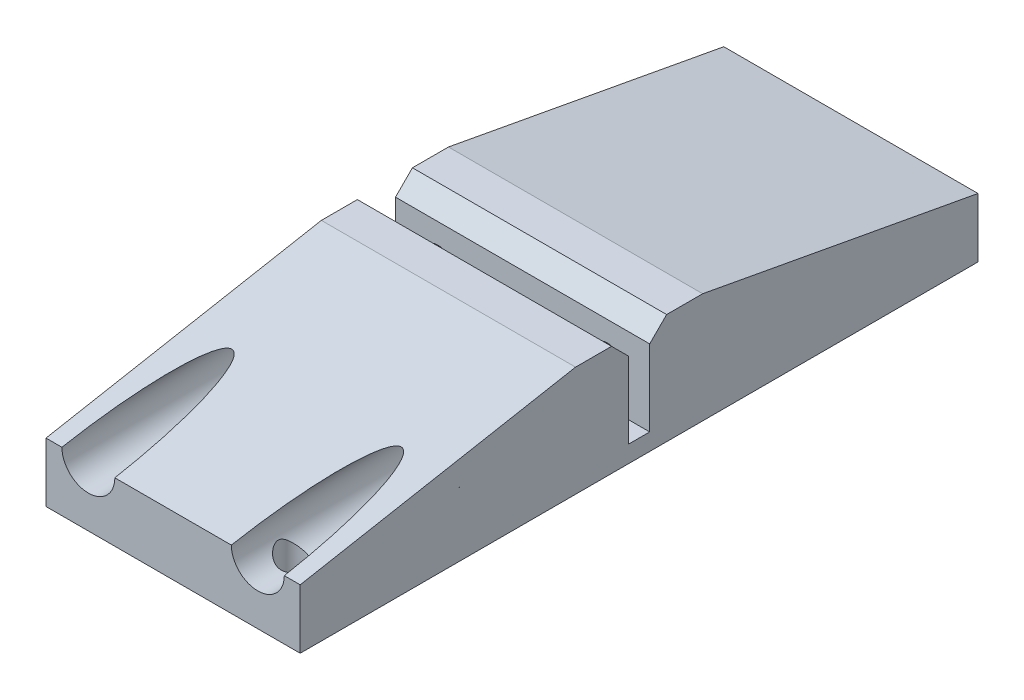
SolidWorks part; units mm, degrees
ref_plane "Front Plane" through (0, 0, 0) normal (0, 0, 1) x (1, 0, 0)
ref_plane "Top Plane" through (0, 0, 0) normal (0, 1, 0) x (1, 0, 0)
ref_plane "Right Plane" through (0, 0, 0) normal (1, 0, 0) x (0, 0, -1)
sketch "Sketch1" plane through (0, 0, 0) normal (0, 1, 0) x (1, 0, 0)
  line L0 (-19.05, 44.45) -> (19.05, 44.45) construction
  line L1 (-19.05, 50.8) -> (19.05, 50.8)
  line L2 (-19.05, 50.8) -> (-19.05, -50.8)
  line L3 (-19.05, -50.8) -> (19.05, -50.8)
  line L4 (19.05, 50.8) -> (19.05, -50.8)
  line L5 (-19.05, 50.8) -> (19.05, -50.8) construction
  line L6 (-19.05, -50.8) -> (19.05, 50.8) construction
  line L7 (19.05, -44.45) -> (-19.05, -44.45) construction
  circle A0 centre (-1.27, 44.45) radius 2.032
  circle A1 centre (11.43, 44.45) radius 2.032
  circle A2 centre (-1.27, -44.45) radius 2.032
  circle A3 centre (11.43, -44.45) radius 2.032
  point P0 (0, 0)
  dimension "D5" = 4.064
  dimension "D6" = 12.7
  dimension "D7" = 17.78
  dimension "D8" = 12.7
  dimension "D9" = 17.78
  dimension "D1" = 101.6
  dimension "D2" = 38.1
  dimension "D3" = 6.35
  dimension "D4" = 6.35
extrude "Boss-Extrude1" add sketch "Sketch1" along normal blind 16.51 contours L2 L3 L4 L1
extrude "Cut-Extrude1" cut sketch "Sketch1<3>" along normal blind 9.525 contours A2 | A0 | A1 | A3
sketch "Sketch1<3>" plane through (0, 0, 0) normal (0, 1, 0) x (1, 0, 0) same geometry as "Sketch1"
sketch "Sketch2" plane through (19.05, 0, 0) normal (1, 0, 0) x (0, 0, -1)
  line L0 (-50.8, 8.89) -> (-9.525, 16.51)
  line L1 (-50.8, 16.51) -> (-50.8, 0) construction
  line L2 (50.8, 16.51) -> (-50.8, 16.51) construction
  line L3 (9.525, 16.51) -> (50.8, 8.89)
  line L4 (50.8, 16.51) -> (50.8, 0) construction
  line L11 (-50.8, 8.89) -> (-50.8, 0)
  line L12 (50.8, 8.89) -> (50.8, 0)
  line L15 (-50.8, 0) -> (50.8, 0)
  line L16 (50.8, 0) -> (50.8, 16.51)
  line L17 (50.8, 16.51) -> (-50.8, 16.51)
  line L18 (-50.8, 16.51) -> (-50.8, 0)
  line L19 (-50.8, 0) -> (50.8, 0)
  line L20 (50.8, 0) -> (50.8, 16.51)
  line L21 (50.8, 16.51) -> (-50.8, 16.51)
  line L22 (-50.8, 16.51) -> (-50.8, 0)
  line M8 (50.8, 0) -> (50.8, 16.51)
  line M9 (50.8, 16.51) -> (-50.8, 16.51)
  line M10 (-50.8, 16.51) -> (-50.8, 0)
  dimension "D1" = 19.05
  dimension "D2" = 8.89
  dimension "D4" = 0
extrude "Cut-Extrude2" cut sketch "Sketch2" against normal through all and the other way through all contours L0 M10 M9 | L3 M9 M8 region at (19.05, 13.97, 37.0417) region at (19.05, 13.97, -37.0417)
sketch "Sketch3" plane through (0, 16.51, 0) normal (0, 1, 0) x (1, 0, 0)
  line L0 (19.05, 0) -> (-19.05, 0) construction
  line L1 (19.05, 1.5875) -> (-19.05, 1.5875)
  line L2 (19.05, -1.5875) -> (-19.05, -1.5875)
  line L4 (-19.05, 9.525) -> (-19.05, -9.525)
  line L5 (-19.05, -9.525) -> (19.05, -9.525)
  line L6 (19.05, -9.525) -> (19.05, 9.525)
  line L7 (19.05, 9.525) -> (-19.05, 9.525)
  line L8 (-19.05, 9.525) -> (-19.05, -9.525)
  line L9 (-19.05, -9.525) -> (19.05, -9.525)
  line L10 (19.05, -9.525) -> (19.05, 9.525)
  line L11 (19.05, 9.525) -> (-19.05, 9.525)
  line M6 (-19.05, 9.525) -> (-19.05, -9.525)
  line M8 (19.05, -9.525) -> (19.05, 9.525)
  dimension "D1" = 0
  dimension "D2" = 1.5875
  dimension "D3" = 1.5875
extrude "Cut-Extrude3" cut sketch "Sketch3" against normal blind 13.97 contours L0 L10 L1 M6 | L0 L8 L2 M8 region at (0, 16.51, 0.7938) region at (0, 16.51, -0.7937)
chamfer "Chamfer1" distance 2.54 angle 45 2 edges at (0, 16.51, 1.5875) (0, 16.51, -1.5875)
sketch "Sketch5" plane through (0, 0, -1.5875) normal (0, 0, 1) x (1, 0, 0)
  line L0 (-19.05, 8.89) -> (19.05, 8.89)
  line L4 (19.05, 2.54) -> (19.05, 13.97)
  line L5 (19.05, 13.97) -> (-19.05, 13.97)
  line L6 (-19.05, 13.97) -> (-19.05, 2.54)
  line L7 (-19.05, 2.54) -> (19.05, 2.54)
  line L8 (19.05, 2.54) -> (19.05, 13.97)
  line L10 (-19.05, 13.97) -> (-19.05, 2.54)
  line L11 (-19.05, 2.54) -> (19.05, 2.54)
  line L14 (19.05, 13.97) -> (-19.05, 13.97)
  circle A0 centre (-12.7, 8.89) radius 3.9688
  circle A1 centre (12.7, 8.89) radius 3.9688
  circle A2 centre (-12.7, 8.89) radius 2.032
  circle A3 centre (12.7, 8.89) radius 2.032
  dimension "D3" = 7.9375
  dimension "D4" = 4.064
  dimension "D2" = 6.35
  dimension "D5" = 25.4
  dimension "D6" = 6.35
  dimension "D1" = 0
extrude "Cut-Extrude4" cut sketch "Sketch5" against normal mid plane 25.4 contours A2 | A3
ref_plane "Plane1" through (0, 0, 4.7625) normal (0, 0, -1) x (-1, 0, 0)
sketch "Sketch6" plane through (0, 0, 4.7625) normal (0, 0, -1) x (-1, 0, 0)
  circle A0 centre (-12.7, 8.89) radius 3.9688 construction
  circle A1 centre (12.7, 8.89) radius 3.9688 construction
  circle A2 centre (-12.7, 8.89) radius 3.9688
  circle A3 centre (12.7, 8.89) radius 3.9688
extrude "Cut-Extrude6" cut sketch "Sketch6" against normal up to next contours A3 | A2
